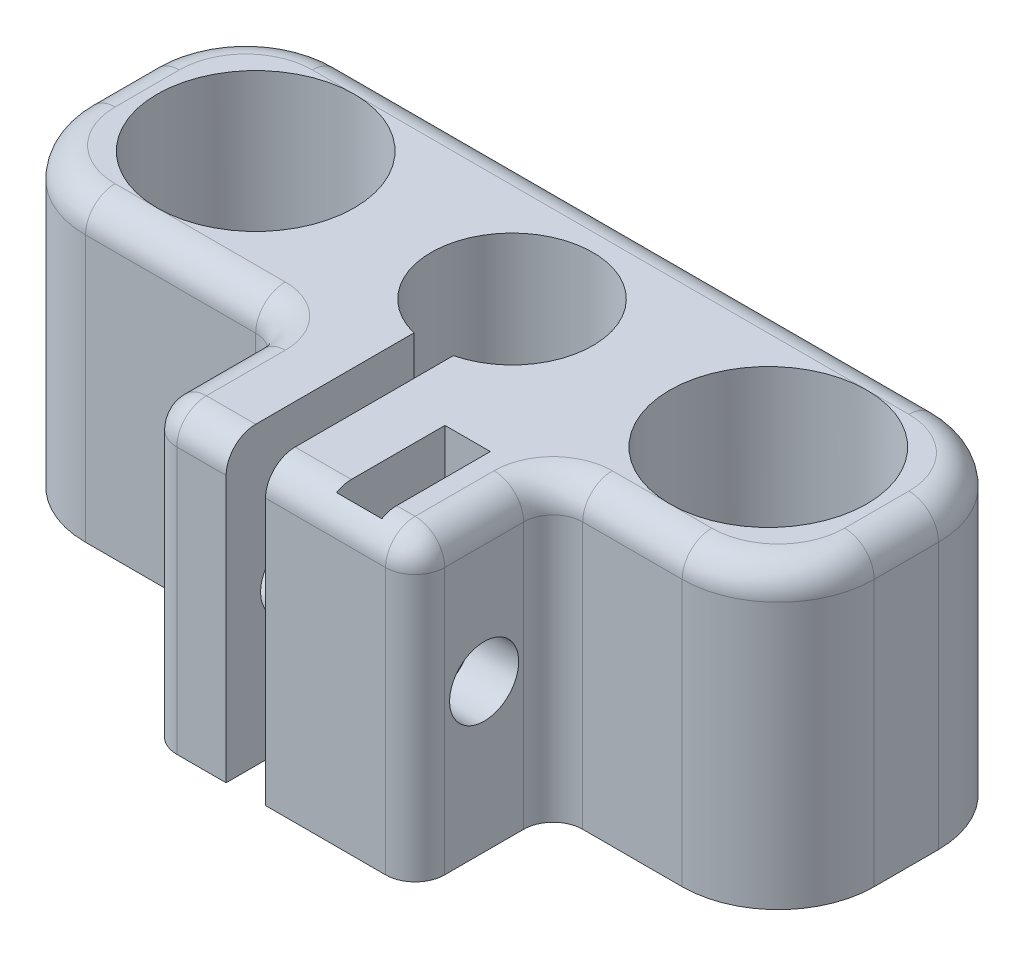
SolidWorks part; units mm, degrees
other "Markup1"
sketch "Sketch3" plane through (17.5, 15, -5.5) normal (0.0562, 0.9983, -0.0177) x (0.9983, -0.0565, -0.0169)
ref_plane "Front Plane" through (0, 0, 0) normal (0, 0, 1) x (1, 0, 0)
ref_plane "Top Plane" through (0, 0, 0) normal (0, 1, 0) x (1, 0, 0)
ref_plane "Right Plane" through (0, 0, 0) normal (1, 0, 0) x (0, 0, -1)
sketch "Sketch1" plane through (0, 0, 0) normal (0, 1, 0) x (1, 0, 0)
  line L0 (0, 6.5) -> (0, -6.5) construction
  line L1 (-15.13, 6.5) -> (15.13, 6.5)
  line L2 (-20, 1.63) -> (-20, -1.63)
  line L3 (-15.13, -6.5) -> (-6.5, -6.5)
  line L4 (20, 1.63) -> (20, -1.63)
  line L5 (-20, 6.5) -> (20, -6.5) construction
  line L6 (-20, -6.5) -> (20, 6.5) construction
  line L7 (1, -13.5) -> (5.5875, -13.5)
  line L9 (-5, -8) -> (-5, -12)
  line L10 (-3.5, -13.5) -> (-1, -13.5)
  line L12 (-1, 0) -> (1, 0)
  line L13 (-1, 0) -> (-1, -13.5)
  line L15 (1, 0) -> (1, -13.5)
  line L16 (10.0875, -6.5) -> (15.13, -6.5)
  line L17 (-5, -6.5) -> (0, -6.5) construction
  line L18 (0, -6.5) -> (5, -6.5) construction
  line L21 (8.5875, -8) -> (8.5875, -12)
  line L22 (7.0875, -13.5) -> (5.5875, -13.5)
  line L23 (6.15, -7.25) -> (3.85, -7.25)
  line L24 (6.15, -7.25) -> (6.15, -12.75)
  line L25 (6.15, -12.75) -> (3.85, -12.75)
  line L26 (3.85, -7.25) -> (3.85, -12.75)
  line L27 (6.15, -7.25) -> (3.85, -12.75) construction
  line L28 (6.15, -12.75) -> (3.85, -7.25) construction
  circle A0 centre (0, 0) radius 4.1
  circle A1 centre (13, 0) radius 2.25
  circle A2 centre (-13, 0) radius 2.25
  arc A3 (15.13, -6.5) -> (20, -1.63) centre (15.13, -1.63) ccw
  arc A4 (15.13, 6.5) -> (20, 1.63) centre (15.13, 1.63) cw
  arc A5 (-15.13, 6.5) -> (-20, 1.63) centre (-15.13, 1.63) ccw
  arc A6 (-20, -1.63) -> (-15.13, -6.5) centre (-15.13, -1.63) ccw
  arc A8 (-6.5, -6.5) -> (-5, -8) centre (-6.5, -8) cw
  arc A10 (-5, -12) -> (-3.5, -13.5) centre (-3.5, -12) ccw
  arc A11 (8.5875, -12) -> (7.0875, -13.5) centre (7.0875, -12) cw
  arc A12 (10.0875, -6.5) -> (8.5875, -8) centre (10.0875, -8) ccw
  point P0 (0, 0)
  point P27 (5, -10)
  point P35 (0, 0)
  point P43 (5, -13.5)
  point P46 (-5, -13.5)
  point P49 (8.5875, -13.5)
  point P55 (8.5875, -10)
  dimension "D1" = 8.2
  dimension "D2" = 4.5
  dimension "D6" = 4.87
  dimension "D10" = 3
  dimension "D12" = 1.5
  dimension "D13" = 2.3
  dimension "D3" = 40
  dimension "D4" = 13
  dimension "D5" = 13
  dimension "D7" = 7
  dimension "D8" = 10
  dimension "D9" = 2
  dimension "D11" = 4.5875
  dimension "D14" = 5.5
extrude "Boss-Extrude1" add sketch "Sketch1" along normal blind 15 contours L9 A10 L10 L13 A0 L15 L7 L16 A3 L4 A4 L1 A5 L2 A6 L3 A8 A2 A1 region at (0, 0, -6.0528)
sketch "Sketch2" plane through (5, 0, 0) normal (1, 0, 0) x (0, 0, -1)
  line L1 (-1.63, 15) -> (-1.63, 0) construction
  line L3 (-8, 15) -> (-12, 15) construction
  circle A0 centre (-10, 7.5) radius 1.75
  point P5 (-10, 15)
  point P10 (-1.63, 7.5)
  dimension "D1" = 3.5
extrude "Cut-Extrude1" cut sketch "Sketch2" against normal through all both and the other way through all
fillet "Fillet2" radius 1.5 17 edges at (4.0437, 15, 13.5) (12.6087, 15, 6.5) (18.5736, 15, 5.0736) (20, 15, 0) (18.5736, 15, -5.0736) (0, 15, -6.5) (-18.5736, 15, -5.0736) (-20, 15, 0) (-2.25, 15, 13.5) (-4.5607, 15, 13.0607) (-5, 15, 10) (-5.4393, 15, 6.9393) (-18.5736, 15, 5.0736) (-10.815, 15, 6.5) (8.1481, 15, 13.0607) (8.5875, 15, 10) (9.0268, 15, 6.9393)
sketch "Sketch4" plane through (0, 15, 0) normal (0, 1, 0) x (1, 0, 0)
  line L0 (0, 0) -> (0, 5) construction
  line L1 (15.13, 5) -> (-15.13, 5) construction
  circle A0 centre (-13, 0) radius 5
  circle A2 centre (13, 0) radius 5
  dimension "D1" = 10
extrude "Cut-Extrude2" cut sketch "Sketch4" against normal offset from surface (10 mm away) 5 up to face at (0.7175, 0, 5.3438)
